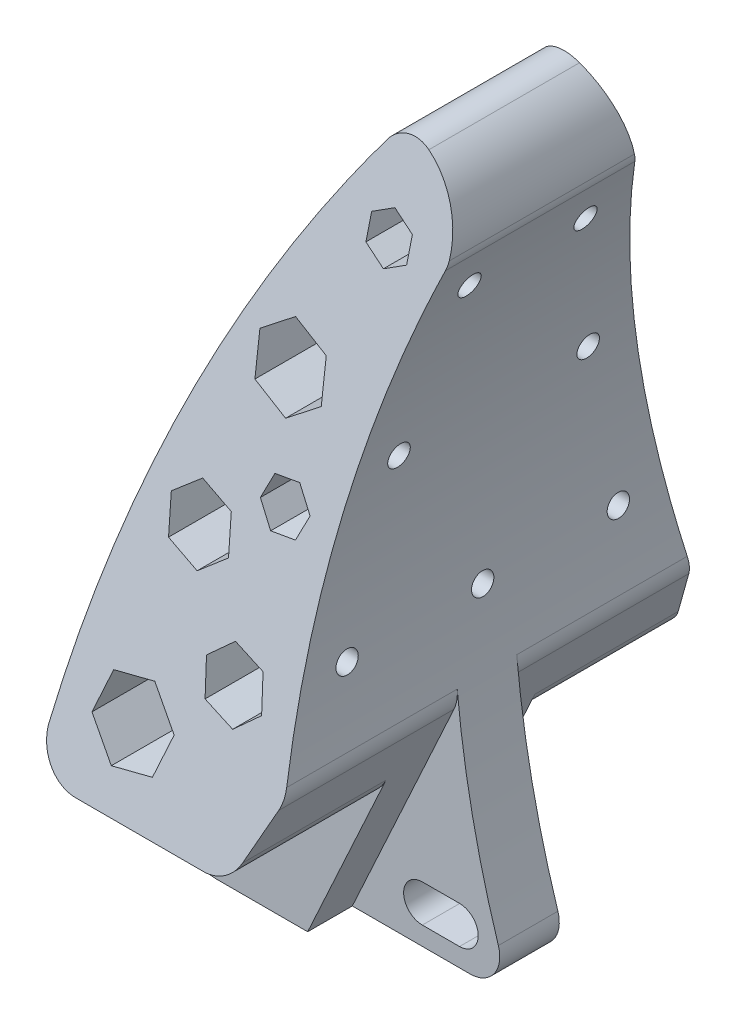
SolidWorks part; units mm, degrees
material "Polylactide (PLA)"
ref_plane "Front Plane" through (0, 0, 0) normal (0, 0, 1) x (1, 0, 0)
ref_plane "Top Plane" through (0, 0, 0) normal (0, 1, 0) x (1, 0, 0)
ref_plane "Right Plane" through (0, 0, 0) normal (1, 0, 0) x (0, 0, -1)
sketch "Sketch5" plane through (0, 0, 0) normal (0, 0, 1) x (1, 0, 0)
  line L0 (-5.5914, 0) -> (-33.738, 0)
  line L8 (-23.7932, 26.0296) -> (-22.1489, 31.13)
  line L9 (-22.1489, 31.13) -> (-25.7438, 35.1043)
  line L10 (-25.7438, 35.1043) -> (-30.9831, 33.9782)
  line L11 (-30.9831, 33.9782) -> (-32.6275, 28.8777)
  line L12 (-32.6275, 28.8777) -> (-29.0326, 24.9034)
  line L13 (-29.0326, 24.9034) -> (-23.7932, 26.0296)
  line L14 (-19.7045, 50.5377) -> (-20.4487, 55.0061)
  line L15 (-20.4487, 55.0061) -> (-24.6905, 56.5958)
  line L16 (-24.6905, 56.5958) -> (-28.1882, 53.7172)
  line L17 (-28.1882, 53.7172) -> (-27.444, 49.2488)
  line L18 (-27.444, 49.2488) -> (-23.2022, 47.6591)
  line L19 (-23.2022, 47.6591) -> (-19.7045, 50.5377)
  line L20 (-12.0209, 69.6144) -> (-12.6014, 74.6171)
  line L21 (-12.6014, 74.6171) -> (-17.2242, 76.6158)
  line L22 (-17.2242, 76.6158) -> (-21.2664, 73.6117)
  line L23 (-21.2664, 73.6117) -> (-20.6859, 68.6089)
  line L24 (-20.6859, 68.6089) -> (-16.0632, 66.6103)
  line L25 (-16.0632, 66.6103) -> (-12.0209, 69.6144)
  line L26 (-4.9947, 87.3663) -> (-5.0097, 90.5214)
  line L27 (-5.0097, 90.5214) -> (-7.7495, 92.0859)
  line L28 (-7.7495, 92.0859) -> (-10.4745, 90.4954)
  line L29 (-10.4745, 90.4954) -> (-10.4595, 87.3403)
  line L30 (-10.4595, 87.3403) -> (-7.7196, 85.7757)
  line L31 (-7.7196, 85.7757) -> (-4.9947, 87.3663)
  line L32 (-12.0209, 37.6377) -> (-12.8753, 41.812)
  line L33 (-12.8753, 41.812) -> (-16.9175, 43.1593)
  line L34 (-16.9175, 43.1593) -> (-20.1054, 40.3322)
  line L35 (-20.1054, 40.3322) -> (-19.251, 36.1579)
  line L36 (-19.251, 36.1579) -> (-15.2088, 34.8106)
  line L37 (-15.2088, 34.8106) -> (-12.0209, 37.6377)
  line L44 (-12.0209, 55.801) -> (-10.8206, 58.8278)
  line L45 (-10.8206, 58.8278) -> (-12.8417, 61.3807)
  line L46 (-12.8417, 61.3807) -> (-16.0632, 60.9068)
  line L47 (-16.0632, 60.9068) -> (-17.2635, 57.88)
  line L48 (-17.2635, 57.88) -> (-15.2423, 55.3271)
  line L49 (-15.2423, 55.3271) -> (-12.0209, 55.801)
  arc A0 (-38.7378, 4.9662) -> (-10.2446, 98.071) centre (124.0248, 6.0676) cw
  arc A1 (-4.9947, 99.3023) -> (0.0615, 90.0404) centre (-9.8234, 90.6553) cw
  arc A2 (-0.1684, 88.9308) -> (-1.7795, 5.2121) centre (122.394, 44.6973) ccw
  arc A3 (-33.738, 0) -> (-38.7378, 4.9662) centre (-33.738, 5) cw
  arc A4 (-1.7795, 5.2121) -> (-5.5914, 0) centre (-5.5914, 4) cw
  arc A5 (-10.2446, 98.071) -> (-4.9947, 99.3023) centre (-6.9449, 95.81) cw
  arc A6 (0.0615, 90.0404) -> (-0.1684, 88.9308) centre (-3.9308, 90.2887) cw
  circle A8 centre (-27.3882, 30.0039) radius 4.641 construction
  circle A9 centre (-23.9464, 52.1275) radius 3.923 construction
  circle A10 centre (-16.6437, 71.613) radius 4.3616 construction
  circle A11 centre (-7.7346, 88.9308) radius 2.7324 construction
  circle A12 centre (-16.0632, 38.985) radius 3.69 construction
  circle A14 centre (-14.042, 58.3539) radius 2.8199 construction
  point P12 (0, 0)
  dimension "D1" = 5
  dimension "D2" = 4
  dimension "D3" = 4
  dimension "D4" = 4
  dimension "D5" = 98.071
extrude "Boss-Extrude4" add sketch "Sketch5" along normal blind 60
sketch "Sketch7" plane through (0, 0, 60) normal (0, 0, 1) x (1, 0, 0)
  line L1 (-12, 5) -> (-7, 5) construction
  line L2 (-12, 7.5121) -> (-7, 7.5121)
  line L3 (-12, 2.4879) -> (-7, 2.4879)
  arc A2 (-12, 7.5121) -> (-12, 2.4879) centre (-12, 5) ccw
  arc A3 (-7, 2.4879) -> (-7, 7.5121) centre (-7, 5) ccw
  point P6 (-9.5, 5)
  dimension "D1" = 5
  dimension "D2" = 2.5121
  dimension "D3" = 7
extrude "Cut-Extrude2" cut sketch "Sketch7" against normal blind 60
sketch "Sketch8" plane through (0, 0, 60) normal (0, 0, 1) x (1, 0, 0)
  circle A0 centre (-32.2838, 6.1708) radius 2.5
  dimension "D1" = 5
extrude "Cut-Extrude3" cut sketch "Sketch8" against normal blind 60
sketch "Sketch9" plane through (0, 0, 0) normal (0, 0, 1) x (1, 0, 0)
  line L0 (0, 0) -> (-21.41, 0)
  line L1 (-33.738, 0) -> (-5.5914, 0) construction
  line L2 (-21.41, 0) -> (-7.1806, 30.9654)
  line L3 (-7.1806, 30.9654) -> (0, 0)
  arc A0 (-0.1684, 88.9308) -> (-1.7795, 5.2121) centre (122.394, 44.6973) ccw construction
  dimension "D1" = 21.41
  dimension "D2" = 65.32
extrude "Cut-Extrude4" cut sketch "Sketch9" along normal blind 26
sketch "Sketch10" plane through (0, 0, 60) normal (0, 0, 1) x (1, 0, 0)
  line L0 (0, 0) -> (-21.41, 0)
  line L1 (-33.738, 0) -> (-5.5914, 0) construction
  line L2 (-21.41, 0) -> (-7.1806, 30.9654)
  line L3 (-7.1806, 30.9654) -> (0, 0)
  arc A0 (-0.1684, 88.9308) -> (-1.7795, 5.2121) centre (122.394, 44.6973) ccw construction
  dimension "D1" = 65.32
  dimension "D2" = 21.41
extrude "Cut-Extrude5" cut sketch "Sketch10" against normal blind 26
sketch "Sketch11" plane through (0, 0, 60) normal (0, 0, 1) x (1, 0, 0)
  line L6 (-44.1103, 20) -> (0, 20)
  line L7 (-44.1103, 20) -> (-44.1103, -3.9253)
  line L8 (-44.1103, -3.9253) -> (0, -3.9253)
  line L9 (0, 20) -> (0, -3.9253)
extrude "Cut-Extrude6" cut sketch "Sketch11" against normal blind 20
sketch "Sketch12" plane through (0, 0, 0) normal (0, 0, -1) x (-1, 0, 0)
  line L6 (40.6681, 20) -> (0, 20)
  line L7 (40.6681, 20) -> (40.6681, -4.8256)
  line L8 (40.6681, -4.8256) -> (0, -4.8256)
  line L9 (0, 20) -> (0, -4.8256)
extrude "Cut-Extrude7" cut sketch "Sketch12" against normal blind 20
fillet "Fillet1" radius 5 1 edges at (-12.2195, 20, 50)
fillet "Fillet2" radius 5 1 edges at (-7.1806, 30.9654, 47)
fillet "Fillet3" radius 5 1 edges at (-12.2195, 20, 10)
fillet "Fillet4" radius 5 1 edges at (-7.1806, 30.9654, 13)
fillet "Fillet5" radius 5 1 edges at (-38.1442, 20, 10)
fillet "Fillet6" radius 5 1 edges at (-38.1442, 20, 50)
sketch "Sketch15" plane through (0, 0, 0) normal (1, 0, 0) x (0, 0, -1)
  line L0 (-60, 20) -> (-40, 99.81)
  line L5 (-60, 20) -> (-60, 99.81)
  line L6 (-60, 99.81) -> (-40, 99.81)
extrude "Cut-Extrude8" cut sketch "Sketch15" against normal blind 53
extrude "Cut-Extrude9" cut sketch "Sketch15<2>" along normal blind 40
sketch "Sketch15<2>" plane through (0, 0, 0) normal (1, 0, 0) x (0, 0, -1) same geometry as "Sketch15"
sketch "Sketch16" plane through (0, 0, 0) normal (1, 0, 0) x (0, 0, -1)
  line L0 (0, 20) -> (0, 99.81)
  line L5 (0, 99.81) -> (-20, 99.81)
  line L6 (0, 20) -> (-20, 99.81)
extrude "Cut-Extrude10" cut sketch "Sketch16" against normal blind 40
extrude "Cut-Extrude11" cut sketch "Sketch16<2>" along normal blind 49
sketch "Sketch16<2>" plane through (0, 0, 0) normal (1, 0, 0) x (0, 0, -1) same geometry as "Sketch16"
sketch "Sketch17" plane through (0, 0, 0) normal (1, 0, 0) x (0, 0, -1)
  line L0 (-56.9193, 32.2933) -> (-34, 32.2933) construction
  line L1 (-42.7263, 88.9308) -> (-56.9193, 32.2933) construction
  circle A0 centre (-48.2279, 42.2933) radius 1.5
  dimension "D1" = 10
  dimension "D2" = 3
  dimension "D3" = 6
extrude "Cut-Extrude12" cut sketch "Sketch17" against normal blind 20
sketch "Sketch18" plane through (0, 0, 0) normal (1, 0, 0) x (0, 0, -1)
  line L0 (-26, 32.2933) -> (-3.0807, 32.2933) construction
  line L1 (-3.0807, 32.2933) -> (-17.2737, 88.9308) construction
  circle A0 centre (-11.7721, 42.2933) radius 1.5
  dimension "D1" = 10
  dimension "D2" = 6
  dimension "D3" = 3
extrude "Cut-Extrude13" cut sketch "Sketch18" against normal blind 20
sketch "Sketch20" plane through (0, 0, 0) normal (1, 0, 0) x (0, 0, -1)
  line L0 (-56.9193, 32.2933) -> (-34, 32.2933) construction
  line L1 (-42.7263, 88.9308) -> (-56.9193, 32.2933) construction
  line L2 (-3.0807, 32.2933) -> (-17.2737, 88.9308) construction
  circle A0 centre (-30.0032, 42.2933) radius 1.5
  dimension "D1" = 10
  dimension "D2" = 23.678
  dimension "D3" = 23.6843
  dimension "D4" = 3
extrude "Cut-Extrude14" cut sketch "Sketch20" against normal blind 20
sketch "Sketch21" plane through (0, 0, 0) normal (1, 0, 0) x (0, 0, -1)
  line L0 (-56.9193, 32.2933) -> (-34, 32.2933) construction
  line L1 (-42.7263, 88.9308) -> (-56.9193, 32.2933) construction
  circle A0 centre (-42.7148, 64.2933) radius 1.5
  dimension "D1" = 32
  dimension "D2" = 6
  dimension "D3" = 3
extrude "Cut-Extrude15" cut sketch "Sketch21" against normal blind 20
sketch "Sketch22" plane through (0, 0, 0) normal (1, 0, 0) x (0, 0, -1)
  line L0 (-26, 32.2933) -> (-3.0807, 32.2933) construction
  line L1 (-3.0807, 32.2933) -> (-17.2737, 88.9308) construction
  circle A0 centre (-17.2852, 64.2933) radius 1.5
  dimension "D1" = 32
  dimension "D2" = 6
  dimension "D3" = 3
extrude "Cut-Extrude16" cut sketch "Sketch22" against normal blind 20
sketch "Sketch23" plane through (0, 0, 0) normal (1, 0, 0) x (0, 0, -1)
  line L0 (-42.7263, 88.9308) -> (-17.2737, 88.9308) construction
  line L1 (-42.7263, 88.9308) -> (-56.9193, 32.2933) construction
  circle A0 centre (-37.7937, 83.9308) radius 1.5
  dimension "D1" = 5
  dimension "D2" = 6
  dimension "D3" = 3
extrude "Cut-Extrude17" cut sketch "Sketch23" against normal blind 15
sketch "Sketch24" plane through (0, 0, 0) normal (1, 0, 0) x (0, 0, -1)
  line L0 (-42.7263, 88.9308) -> (-17.2737, 88.9308) construction
  line L1 (-3.0807, 32.2933) -> (-17.2737, 88.9308) construction
  circle A0 centre (-22.2063, 83.9308) radius 1.5
  dimension "D1" = 5
  dimension "D2" = 6
  dimension "D3" = 3
extrude "Cut-Extrude18" cut sketch "Sketch24" against normal blind 15
